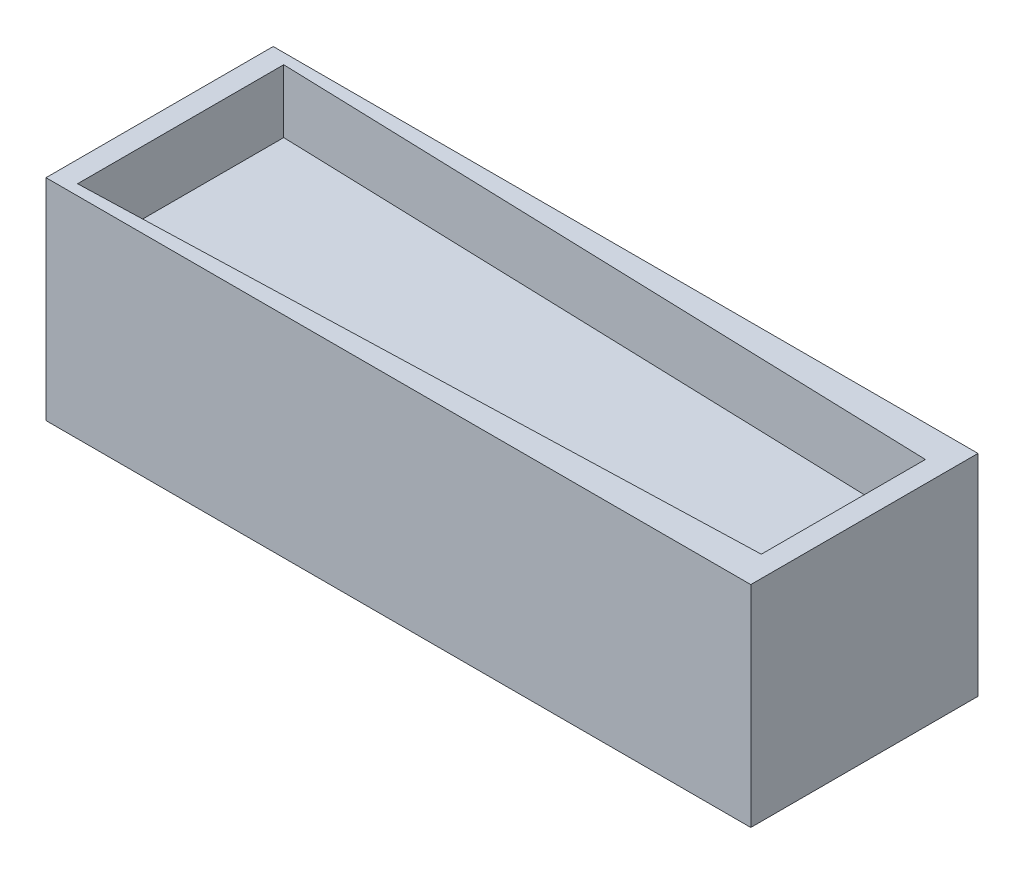
SolidWorks part; units mm, degrees
ref_plane "Front Plane" through (0, 0, 0) normal (0, 0, 1) x (1, 0, 0)
ref_plane "Top Plane" through (0, 0, 0) normal (0, 1, 0) x (1, 0, 0)
ref_plane "Right Plane" through (0, 0, 0) normal (1, 0, 0) x (0, 0, -1)
sketch "Sketch2" plane through (0, 0, 0) normal (0, 1, 0) x (1, 0, 0)
  line L1 (-167.5, 54) -> (167.5, 54)
  line L2 (-167.5, 54) -> (-167.5, -54)
  line L3 (-167.5, -54) -> (167.5, -54)
  line L4 (167.5, 54) -> (167.5, -54)
  line L5 (-167.5, 54) -> (167.5, -54) construction
  line L6 (-167.5, -54) -> (167.5, 54) construction
  point P0 (0, 0)
  dimension "D1" = 335
  dimension "D2" = 108
extrude "Boss-Extrude4" add sketch "Sketch2" against normal blind 100
sketch "Sketch3" plane through (0, 0, 0) normal (0, 1, 0) x (1, 0, 0)
  line L0 (-157.5, -49) -> (-157.5, 49)
  line L1 (157.5, -39) -> (157.5, 39)
  line L2 (-175, 0) -> (175, 0) construction
  line L3 (-157.5, 49) -> (157.5, 39)
  line L4 (157.5, -39) -> (-157.5, -49)
  line L5 (-167.5, 54) -> (-167.5, -54) construction
  line L6 (167.5, -54) -> (167.5, 54) construction
  point P3 (-157.5, 0)
  point P9 (157.5, 0)
  dimension "D1" = 98
  dimension "D2" = 78
  dimension "D3" = 10
  dimension "D4" = 10
  dimension "D5" = 315
extrude "Cut-Extrude1" cut sketch "Sketch3" against normal blind 30 contours L3 L1 L4 L0
sketch "Sketch4" plane through (0, -100, 0) normal (0, -1, 0) x (-1, 0, 0)
  line L1 (150, -50) -> (-150, -50)
  line L2 (150, -50) -> (150, 50)
  line L3 (150, 50) -> (-150, 50)
  line L4 (-150, -50) -> (-150, 50)
  dimension "D1" = 300
  dimension "D2" = 100
extrude "Cut-Extrude2" cut sketch "Sketch4" against normal blind 68 contours L2 L3 L4 L1
